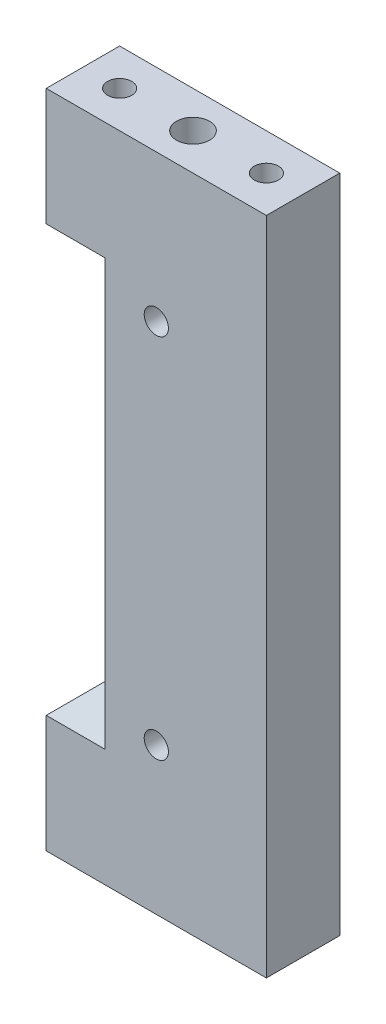
SolidWorks part; units mm, degrees
ref_plane "Front Plane" through (0, 0, 0) normal (0, 0, 1) x (1, 0, 0)
ref_plane "Top Plane" through (0, 0, 0) normal (0, 1, 0) x (1, 0, 0)
ref_plane "Right Plane" through (0, 0, 0) normal (1, 0, 0) x (0, 0, -1)
sketch "Sketch1" plane through (0, 0, 0) normal (0, 1, 0) x (1, 0, 0)
  line L1 (-15, -5) -> (15, -5)
  line L2 (-15, -5) -> (-15, 5)
  line L3 (-15, 5) -> (15, 5)
  line L4 (15, -5) -> (15, 5)
  line L5 (-15, -5) -> (15, 5) construction
  line L6 (-15, 5) -> (15, -5) construction
  point P0 (0, 0)
  dimension "D1" = 30
  dimension "D2" = 10
extrude "Boss-Extrude1" add sketch "Sketch1" along normal blind 90
hole_wizard "M4x0.7 Tapped Hole1" positions "Sketch2" profile "Sketch4" tap size "M4x0.7" standard "ANSI Metric"
sketch "Sketch2" plane through (0, 0, 0) normal (0, -1, 0) x (-1, 0, 0)
  line L0 (-10, 0) -> (10, 0)
  point P1 (-10, 0)
  point P2 (10, 0)
  point P8 (0, 0)
  dimension "D1" = 20
sketch "Sketch4" plane through (10, 0, 0) normal (1, 0, 0) x (0, 0, -1)
  line L0 (0, 0) -> (0, 15.9914)
  line L1 (0, 15.9914) -> (1.65, 15)
  line L2 (1.65, 15) -> (1.65, 0)
  line L5 (1.65, 0) -> (0, 0)
  line L10 (0, 15.9914) -> (-1.65, 15) construction
  line L11 (0, -6.35) -> (0, 107.95) construction
  dimension "Tap Drill Dia." = 3.3
  dimension "Tap Drill Depth" = 15
  dimension "Drill Angle" = 118
cosmetic thread "Hole Thread1" parameters "D1"=15, "D2"=4
cosmetic thread "Hole Thread2" parameters "D1"=15, "D2"=4
cosmetic thread "Hole Thread7" parameters "D1"=15, "D2"=4
hole_wizard "M4x0.7 Tapped Hole2" positions "Sketch5" profile "Sketch6" tap size "M4x0.7" standard "ANSI Metric"
sketch "Sketch5" plane through (0, 90, 0) normal (0, 1, 0) x (1, 0, 0)
  line L0 (-10, 0) -> (10, 0)
  point P1 (-10, 0)
  point P2 (10, 0)
  point P5 (0, 0)
  dimension "D1" = 20
sketch "Sketch6" plane through (-10, 90, 0) normal (1, 0, 0) x (0, 0, 1)
  line L0 (0, 0) -> (0, 15.9914)
  line L1 (0, 15.9914) -> (1.65, 15)
  line L2 (1.65, 15) -> (1.65, 0)
  line L5 (1.65, 0) -> (0, 0)
  line L10 (0, 15.9914) -> (-1.65, 15) construction
  line L11 (0, -6.35) -> (0, 107.95) construction
  dimension "Tap Drill Dia." = 3.3
  dimension "Tap Drill Depth" = 15
  dimension "Drill Angle" = 118
cosmetic thread "Hole Thread3" parameters "D1"=14.3, "D2"=4
cosmetic thread "Hole Thread4" parameters "D1"=14.3, "D2"=4
hole_wizard "M4x0.7 Tapped Hole3" positions "Sketch7" profile "Sketch9" tap size "M4x0.7" standard "ANSI Metric" end condition through all
sketch "Sketch7" plane through (0, 0, 5) normal (0, 0, 1) x (1, 0, 0)
  point P0 (0, 70)
  point P2 (0, 20)
  dimension "D1" = 20
  dimension "D2" = 20
sketch "Sketch9" plane through (0, 70, 5) normal (1, 0, 0) x (0, -1, 0)
  line L0 (0, 0) -> (0, 10)
  line L1 (0, 10) -> (1.65, 10)
  line L2 (1.65, 10) -> (1.65, 0)
  line L5 (1.65, 0) -> (0, 0)
  line L11 (0, -6.35) -> (0, 107.95) construction
  dimension "Thru Tap Drill Dia." = 3.3
  dimension "Thru Tap Drill Depth" = 10
cosmetic thread "Hole Thread5" parameters "D2"=4
cosmetic thread "Hole Thread6" parameters "D2"=4
hole_wizard "M4 Clearance Hole1" positions "Sketch10" profile "Sketch12" hole size "M4" standard "ANSI Metric"
sketch "Sketch10" plane through (0, 90, 0) normal (0, 1, 0) x (1, 0, 0)
  point P0 (0, 0)
sketch "Sketch12" plane through (0, 90, 0) normal (1, 0, 0) x (0, 0, 1)
  line L0 (0, 0) -> (0, 16.3519)
  line L1 (0, 16.3519) -> (2.25, 15)
  line L2 (2.25, 15) -> (2.25, 0)
  line L5 (2.25, 0) -> (0, 0)
  line L10 (0, 16.3519) -> (-2.25, 15) construction
  line L11 (0, -6.35) -> (0, 107.95) construction
  dimension "Hole Dia." = 4.5
  dimension "Hole Depth" = 15
  dimension "Drill Angle" = 118
sketch "Sketch13" plane through (-15, 0, 0) normal (-1, 0, 0) x (0, 0, 1)
  line L0 (-5, 0) -> (5, 0) construction
  line L1 (-3, 20) -> (5, 20)
  line L2 (-3, 20) -> (-3, 70)
  line L3 (-3, 70) -> (5, 70)
  line L4 (5, 20) -> (5, 70)
  line L5 (-3, 20) -> (5, 70) construction
  line L6 (-3, 70) -> (5, 20) construction
  line L7 (5, 90) -> (5, 0) construction
  point P0 (1, 45)
  point P7 (0, 0)
  dimension "D1" = 8
  dimension "D2" = 50
  dimension "D3" = 45
extrude "Cut-Extrude1" cut sketch "Sketch13" against normal blind 8
chamfer "Chamfer4" distance 8 angle 45 1 edges at (-7, 45, -3)
chamfer "Chamfer5" distance 4 angle 45 4 edges at (-11, 20, 5) (-15, 20, 1) (-11, 70, 5) (-15, 70, 1)
